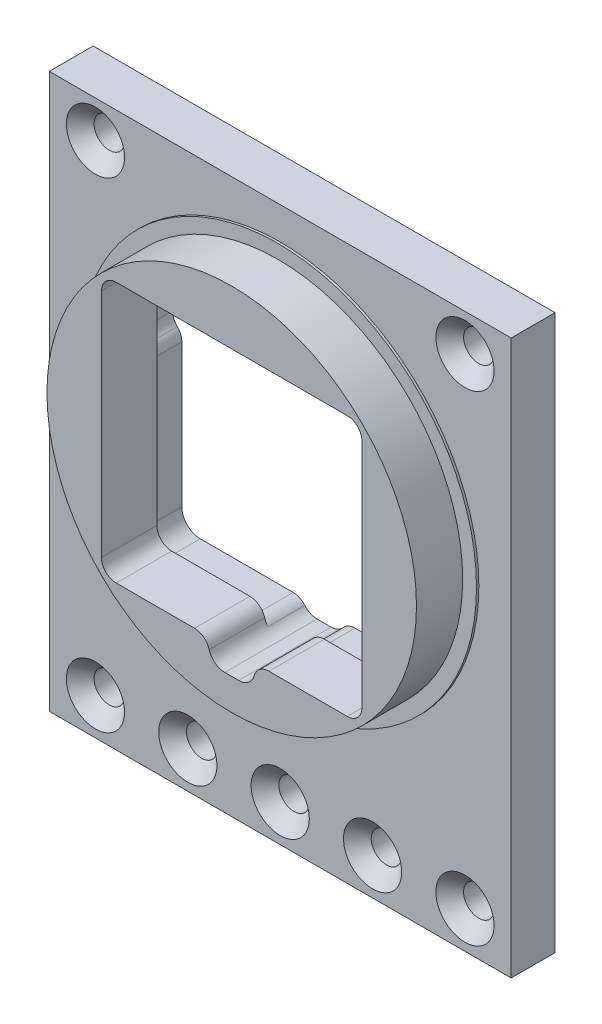
SolidWorks part; units mm, degrees
material "PVC rigide"
ref_plane "Plan de face" through (0, 0, 0) normal (0, 0, 1) x (1, 0, 0)
ref_plane "Plan de dessus" through (0, 0, 0) normal (0, 1, 0) x (1, 0, 0)
ref_plane "Plan de droite" through (0, 0, 0) normal (1, 0, 0) x (0, 0, -1)
sketch "Esquisse1" plane through (0, 0, 0) normal (0, 0, 1) x (1, 0, 0)
  line L1 (28.2, 28.2) -> (-28.2, 28.2)
  line L2 (28.2, 28.2) -> (28.2, -28.2)
  line L3 (28.2, -28.2) -> (-28.2, -28.2)
  line L4 (-28.2, 28.2) -> (-28.2, -28.2)
  line L5 (28.2, 28.2) -> (-28.2, -28.2) construction
  line L6 (28.2, -28.2) -> (-28.2, 28.2) construction
  line L7 (50, 50) -> (-50, 50)
  line L8 (50, 50) -> (50, -50)
  line L9 (50, -50) -> (-50, -50)
  line L10 (-50, 50) -> (-50, -50)
  line L11 (50, 50) -> (-50, -50) construction
  line L12 (50, -50) -> (-50, 50) construction
  circle A0 centre (0, 0) radius 40 construction
  point P0 (0, 0)
  dimension "D2" = 80
  dimension "D1" = 56.4
  dimension "D3" = 100
extrude "Boss.-Extru.1" add sketch "Esquisse1" along normal blind 10
fillet "Congé1" radius 3.2 4 edges at (-28.2, -28.2, 5) (28.2, 28.2, 5) (-28.2, 28.2, 5) (28.2, -28.2, 5)
sketch "Esquisse3" plane through (0, 0, 10) normal (0, 0, 1) x (1, 0, 0)
  line L5 (-28.2, 25) -> (-28.2, -25)
  line L6 (25, 28.2) -> (-25, 28.2)
  line L7 (28.2, -25) -> (28.2, 25)
  line L8 (-25, -28.2) -> (25, -28.2)
  line L9 (-28.2, 25) -> (-28.2, -25)
  line L10 (25, 28.2) -> (-25, 28.2)
  line L11 (28.2, -25) -> (28.2, 25)
  line L12 (-25, -28.2) -> (25, -28.2)
  circle A0 centre (0, 0) radius 40
  arc A5 (-25, 28.2) -> (-28.2, 25) centre (-25, 25) ccw
  arc A6 (28.2, 25) -> (25, 28.2) centre (25, 25) ccw
  arc A7 (25, -28.2) -> (28.2, -25) centre (25, -25) ccw
  arc A8 (-28.2, -25) -> (-25, -28.2) centre (-25, -25) ccw
  arc A9 (-25, 28.2) -> (-28.2, 25) centre (-25, 25) ccw
  arc A10 (28.2, 25) -> (25, 28.2) centre (25, 25) ccw
  arc A11 (25, -28.2) -> (28.2, -25) centre (25, -25) ccw
  arc A12 (-28.2, -25) -> (-25, -28.2) centre (-25, -25) ccw
  dimension "D1" = 80
  dimension "D2" = 0
extrude "Boss.-Extru.2" add sketch "Esquisse3" along normal blind 10
sketch "Esquisse4" plane through (0, 0, 10) normal (0, 0, 1) x (1, 0, 0)
  circle A0 centre (0, 0) radius 43
  circle A2 centre (0, 0) radius 40 construction
  dimension "D1" = 3
extrude "Enlèv. mat.-Extru.2" cut sketch "Esquisse4" against normal blind 0.5 flip side to cut
sketch "Esquisse5" plane through (0, 0, 0) normal (0, 0, -1) x (-1, 0, 0)
  line L1 (30.8, -30.8) -> (-30.8, -30.8)
  line L2 (30.8, -30.8) -> (30.8, 30.8)
  line L3 (30.8, 30.8) -> (-30.8, 30.8)
  line L4 (-30.8, -30.8) -> (-30.8, 30.8)
  line L5 (30.8, -30.8) -> (-30.8, 30.8) construction
  line L6 (30.8, 30.8) -> (-30.8, -30.8) construction
  point P0 (0, 0)
  dimension "D1" = 61.6
extrude "Enlèv. mat.-Extru.3" cut sketch "Esquisse5" against normal blind 9
sketch "Esquisse6" plane through (0, 0, 9) normal (0, 0, -1) x (-1, 0, 0)
  line L4 (-30.8, 30.8) -> (-30.8, -30.8)
  line L5 (-30.8, -30.8) -> (30.8, -30.8)
  line L6 (30.8, -30.8) -> (30.8, 30.8)
  line L7 (30.8, 30.8) -> (-30.8, 30.8)
  line L8 (-30.8, 30.8) -> (-30.8, -30.8)
  line L9 (-30.8, -30.8) -> (30.8, -30.8)
  line L10 (30.8, -30.8) -> (30.8, 30.8)
  line L11 (30.8, 30.8) -> (-30.8, 30.8)
  line L13 (28.2, -25) -> (28.2, 25)
  line L14 (-25, -28.2) -> (25, -28.2)
  line L15 (-28.2, 25) -> (-28.2, -25)
  line L16 (25, 28.2) -> (-25, 28.2)
  line L17 (28.2, -25) -> (28.2, 25)
  line L18 (-25, -28.2) -> (25, -28.2)
  line L19 (-28.2, 25) -> (-28.2, -25)
  line L20 (25, 28.2) -> (-25, 28.2)
  arc A4 (28.2, 25) -> (25, 28.2) centre (25, 25) ccw
  arc A5 (25, -28.2) -> (28.2, -25) centre (25, -25) ccw
  arc A6 (-28.2, -25) -> (-25, -28.2) centre (-25, -25) ccw
  arc A7 (-25, 28.2) -> (-28.2, 25) centre (-25, 25) ccw
  arc A8 (28.2, 25) -> (25, 28.2) centre (25, 25) ccw
  arc A9 (25, -28.2) -> (28.2, -25) centre (25, -25) ccw
  arc A10 (-28.2, -25) -> (-25, -28.2) centre (-25, -25) ccw
  arc A11 (-25, 28.2) -> (-28.2, 25) centre (-25, 25) ccw
  dimension "D1" = 0
  dimension "D2" = 0
extrude "Boss.-Extru.3" add sketch "Esquisse6" along normal blind 1
sketch "Esquisse12" plane through (0, -50, 0) normal (0, -1, 0) x (1, 0, 0)
  line L4 (50, 9.5) -> (-50, 9.5)
  line L5 (-50, 9.5) -> (-50, 0)
  line L6 (-50, 0) -> (50, 0)
  line L7 (50, 0) -> (50, 9.5)
  line L8 (50, 9.5) -> (-50, 9.5)
  line L9 (-50, 9.5) -> (-50, 0)
  line L10 (-50, 0) -> (50, 0)
  line L11 (50, 0) -> (50, 9.5)
  dimension "D1" = 0
extrude "Boss.-Extru.5" add sketch "Esquisse12" along normal blind 20
sketch "Esquisse7" [suppressed] plane through (0, 0, 8) normal (0, 0, -1) x (-1, 0, 0)
  line L5 (-24.5, -28) -> (24.5, -28)
  line L6 (28, -24.5) -> (28, 24.5)
  line L7 (24.5, 28) -> (-24.5, 28)
  line L8 (-28, 24.5) -> (-28, -24.5)
  line L9 (-24.5, -28) -> (24.5, -28)
  line L10 (28, -24.5) -> (28, 24.5)
  line L11 (24.5, 28) -> (-24.5, 28)
  line L12 (-28, 24.5) -> (-28, -24.5)
  circle A0 centre (0, 0) radius 25.05
  arc A5 (24.5, -28) -> (28, -24.5) centre (24.5, -24.5) ccw
  arc A6 (28, 24.5) -> (24.5, 28) centre (24.5, 24.5) ccw
  arc A7 (-24.5, 28) -> (-28, 24.5) centre (-24.5, 24.5) ccw
  arc A8 (-28, -24.5) -> (-24.5, -28) centre (-24.5, -24.5) ccw
  arc A9 (24.5, -28) -> (28, -24.5) centre (24.5, -24.5) ccw
  arc A10 (28, 24.5) -> (24.5, 28) centre (24.5, 24.5) ccw
  arc A11 (-24.5, 28) -> (-28, 24.5) centre (-24.5, 24.5) ccw
  arc A12 (-28, -24.5) -> (-24.5, -28) centre (-24.5, -24.5) ccw
  dimension "D1" = 50.1
  dimension "D2" = 0
extrude "Boss.-Extru.4" [suppressed] add sketch "Esquisse7" against normal up to surface (12 mm away)
sketch "Esquisse10" [suppressed] plane through (0, 0, 8) normal (0, 0, -1) x (-1, 0, 0)
  line L1 (-24.1504, -25.3329) -> (24.1504, -25.3329) construction
  line L2 (-24.1504, -25.3329) -> (-24.1504, 25.3329) construction
  line L3 (-24.1504, 25.3329) -> (24.1504, 25.3329) construction
  line L4 (24.1504, -25.3329) -> (24.1504, 25.3329) construction
  line L5 (-24.1504, -25.3329) -> (24.1504, 25.3329) construction
  line L6 (-24.1504, 25.3329) -> (24.1504, -25.3329) construction
  circle A0 centre (0, 0) radius 35 construction
  point P0 (0, 0)
  dimension "D1" = 70
hole_wizard "Trou taraudé M5x0.81" positions "Esquisse3D2" profile "Esquisse11" tap size "M5x0.8" standard "Ansi Metric"
sketch3d "Esquisse3D2"
  point P0 (24.1504, 25.3329, 8)
  point P3 (24.1504, -25.3329, 8)
  point P6 (-24.1504, 25.3329, 8)
  point P9 (-24.1504, -25.3329, 8)
sketch "Esquisse11" plane through (24.1504, 25.3329, 8) normal (1, 0, 0) x (0, 1, 0)
  line L0 (0, 0) -> (0, 12)
  line L1 (0, 12) -> (2.1, 12)
  line L2 (2.1, 12) -> (2.1, 0)
  line L5 (2.1, 0) -> (0, 0)
  line L11 (0, -6.35) -> (0, 107.95) construction
  dimension "Diamètre principal du filetage" = 4.2
  dimension "Profondeur du trou pour taraudage jusqu'au prochain" = 12
sketch "Esquisse13" plane through (0, 0, 9.5) normal (0, 0, 1) x (1, 0, 0)
  line L0 (-50, -62) -> (50, -62) construction
  line L1 (-50, 50) -> (-50, -70) construction
  line L2 (50, -70) -> (50, 50) construction
  line L3 (50, -70) -> (-50, -70) construction
  line L4 (0, -62) -> (0, -70) construction
  line L5 (-40, -62) -> (-40, -70) construction
  line L6 (40, -62) -> (40, -70) construction
  line L7 (-20, -62) -> (-20, -70) construction
  line L8 (20, -62) -> (20, -70) construction
  line L9 (-50, 42) -> (50, 42) construction
  line L10 (50, 50) -> (-50, 50) construction
  line L11 (-40, -62) -> (-40, 50) construction
  line L12 (40, -62) -> (40, 50) construction
  dimension "D1" = 8
  dimension "D2" = 10
  dimension "D3" = 20
  dimension "D4" = 8
hole_wizard "Fraisage pour vis à tête fraisée M61" positions "Esquisse3D3" profile "Esquisse14" countersink size "M6" standard "Ansi Metric" end condition through all
sketch3d "Esquisse3D3"
  line L0 (-40, -62, 9.5) -> (-40, -70, 9.5) construction
  line L1 (-50, 42, 9.5) -> (50, 42, 9.5) construction
  line L2 (40, -62, 9.5) -> (40, 50, 9.5) construction
  line L3 (-40, -62, 9.5) -> (-40, 50, 9.5) construction
  point P0 (-40, -62, 9.5)
  point P4 (-20, -62, 9.5)
  point P7 (0, -62, 9.5)
  point P10 (20, -62, 9.5)
  point P13 (40, -62, 9.5)
  point P21 (-40, 42, 9.5)
  point P25 (40, 42, 9.5)
sketch "Esquisse14" plane through (-40, -62, 9.5) normal (1, 0, 0) x (0, -1, 0)
  line L0 (0, 0) -> (0, 9.5)
  line L1 (0, 9.5) -> (3.3, 9.5)
  line L2 (3.3, 9.5) -> (3.3, 3)
  line L3 (3.3, 3) -> (6.3, 0)
  line L5 (6.3, 0) -> (0, 0)
  line L6 (-3.3, 3) -> (-6.3, 0) construction
  line L11 (0, -6.35) -> (0, 107.95) construction
  dimension "Diamètre du perçage jusqu'au prochain" = 6.6
  dimension "Profondeur du perçage jusqu'au prochain" = 9.5
  dimension "Diamètre du fraisage entrant" = 12.6
  dimension "Angle du fraisage entrant" = 90
fillet "Congé2" [suppressed] radius 4
sketch "Esquisse16" plane through (0, 0, 0) normal (0, 0, -1) x (-1, 0, 0)
  line L0 (30.8, -30.8) -> (30.8, 30.8) construction
  line L1 (30.8, 15.8) -> (32.8, 15.8)
  line L2 (30.8, 15.8) -> (30.8, 5.8)
  line L3 (30.8, 5.8) -> (32.8, 5.8)
  line L4 (32.8, 15.8) -> (32.8, 5.8)
  line L5 (30.8, 30.8) -> (-30.8, 30.8) construction
  line L6 (-30.8, 30.8) -> (-30.8, -30.8) construction
  line L7 (-30.8, -15.8) -> (-32.8, -15.8)
  line L8 (-30.8, -15.8) -> (-30.8, -5.8)
  line L9 (-30.8, -5.8) -> (-32.8, -5.8)
  line L10 (-32.8, -15.8) -> (-32.8, -5.8)
  line L11 (-30.8, -30.8) -> (30.8, -30.8) construction
  dimension "D1" = 2
  dimension "D2" = 10
  dimension "D3" = 15
  dimension "D4" = 15
  dimension "D5" = 10
  dimension "D6" = 2
extrude "Enlèv. mat.-Extru.4" cut sketch "Esquisse16" against normal up to surface (8 mm away) up to face at (0, 0, 8)
fillet "Congé3" radius 3.5 4 edges at (32.8, -5.8, 4) (32.8, -15.8, 4) (-32.8, 5.8, 4) (-32.8, 15.8, 4)
sketch "Esquisse17" plane through (0, 0, 20) normal (0, 0, 1) x (1, 0, 0)
  line L0 (0, -28.2) -> (0, -40) construction
  line L1 (-25, -28.2) -> (25, -28.2) construction
  line L3 (-5, -28.2) -> (5, -28.2)
  line L4 (-5, -28.2) -> (-5, -33.2)
  line L5 (-5, -33.2) -> (5, -33.2)
  line L6 (5, -28.2) -> (5, -33.2)
  circle A0 centre (0, 0) radius 40 construction
  dimension "D1" = 10
  dimension "D2" = 5
extrude "Enlèv. mat.-Extru.5" cut sketch "Esquisse17" against normal through all
fillet "Congé4" radius 3.5 2 edges at (5, -33.2, 10) (-5, -33.2, 10)
fillet "Congé5" radius 3.3 14 edges at (-30.8, 5.8, 4) (-30.8, 15.8, 4) (30.8, -5.8, 4) (30.8, -15.8, 4) (5, -28.95, 8) (5, -28.2, 14) (-5, -28.2, 14) (-5, -28.95, 20) (5, -28.95, 20) (5, -29.7, 14) (-5, -28.95, 8) (-5, -29.7, 14) (4.8226, -30.8, 4) (-4.8226, -30.8, 4)
fillet "Congé6" radius 4 4 edges at (30.8, -30.8, 4) (30.8, 30.8, 4) (-30.8, 30.8, 4) (-30.8, -30.8, 4)
